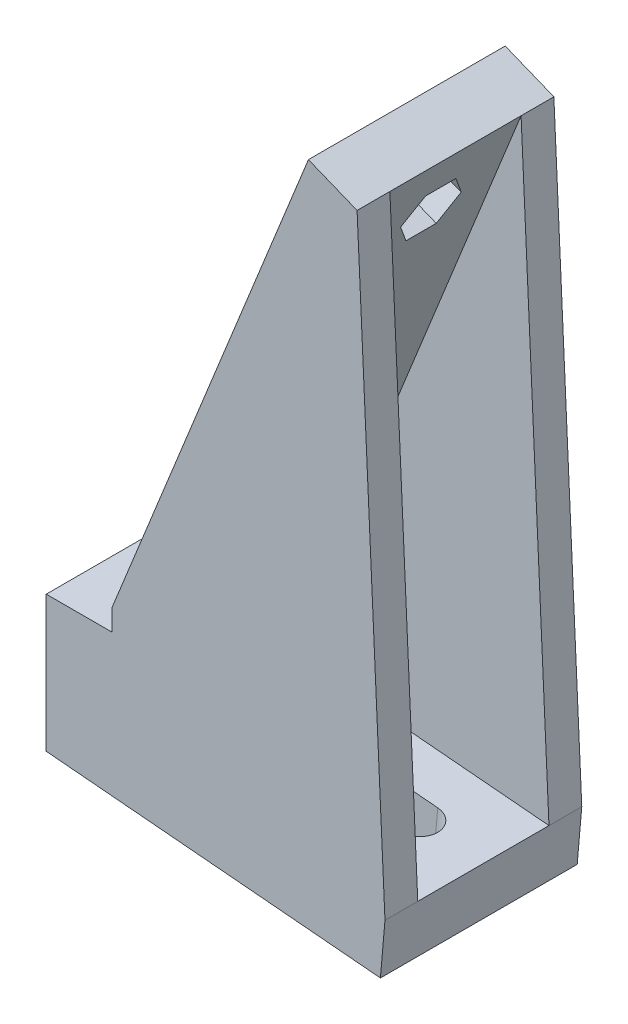
SolidWorks part; units mm, degrees
ref_plane "Front Plane" through (0, 0, 0) normal (0, 0, 1) x (1, 0, 0)
ref_plane "Top Plane" through (0, 0, 0) normal (0, 1, 0) x (1, 0, 0)
ref_plane "Right Plane" through (0, 0, 0) normal (1, 0, 0) x (0, 0, -1)
sketch "Sketch1" plane through (0, 0, 0) normal (0, 0, 1) x (1, 0, 0)
  line L0 (0, 0) -> (29.9685, 74.1747)
  line L3 (65.2738, -16.9226) -> (1.7911, -16.9226) construction
  line L4 (1.7911, -16.9226) -> (37.386, 71.1779)
  line L5 (37.386, 71.1779) -> (29.9685, 74.1747)
  line L7 (0, 0) -> (0, -3.175)
  line L8 (0, -3.175) -> (-10, -3.175)
  line L9 (0, -3.175) -> (-280, -3.175) construction
  line L10 (-10, -3.175) -> (-10, -23.9215)
  line L11 (194.4997, -41.8129) -> (-483.4753, 17.5022) construction
  line L12 (-10, -23.9215) -> (40.9417, -28.3783)
  line L13 (40.9417, -28.3783) -> (41.6389, -20.4088)
  line L15 (1.7911, -16.9226) -> (41.6389, -20.4088)
  dimension "D1" = 8
  dimension "D2" = 68
  dimension "D3" = 8
  dimension "D4" = 80
  dimension "D5" = 10
  dimension "D6" = 40
extrude "Boss-Extrude1" add sketch "Sketch1" along normal mid plane 30
sketch "Sketch2" plane through (-1.0772, -16.6716, 0) normal (0.0872, 0.9962, 0) x (0.9962, -0.0872, 0)
  line L0 (32.8793, 0) -> (27.8793, 0) construction
  line L1 (32.8793, -3) -> (27.8793, -3)
  line L2 (32.8793, 3) -> (27.8793, 3)
  line L4 (42.8793, -15) -> (42.8793, 15) construction
  arc A0 (32.8793, -3) -> (32.8793, 3) centre (32.8793, 0) ccw
  arc A1 (27.8793, 3) -> (27.8793, -3) centre (27.8793, 0) ccw
  point P3 (30.3793, 0)
  dimension "D3" = 3
  dimension "D1" = 5
  dimension "D2" = 10
extrude "Cut-Extrude1" cut sketch "Sketch2" against normal through all
sketch "Sketch3" plane through (7.4175, -2.9969, 0) normal (0.9272, -0.3746, 0) x (0, 0, -1)
sketch "Sketch4" plane through (0, 0, 15) normal (0, 0, 1) x (1, 0, 0)
  line L0 (37.386, 71.1779) -> (41.6389, -20.4088)
  line L1 (40.9417, -28.3783) -> (41.6389, -20.4088) construction
  line L2 (41.6389, -20.4088) -> (1.7911, -16.9226) construction
rib "Rib1" sketch "Sketch4" sketch "Sketch4" thickness 5 extrusion direction parallel to sketch draft on no parameters "D1"=5
mirror "Mirror1" about plane through (0, 0, 0) normal (0, 0, 1) of "Rib1"
sketch "Sketch6" plane through (7.4175, -2.9969, 0) normal (0.9272, -0.3746, 0) x (0, 0, -1)
  line L0 (-10, 80) -> (10, 80) construction
  point P0 (0, 70)
  point P2 (0, 25)
  point P9 (0, 80)
  dimension "D1" = 10
  dimension "D2" = 45
hole_wizard "M4 Clearance Hole1" positions "Sketch6" profile "Sketch7" hole size "M4" standard "ANSI Metric" end condition through all
sketch "Sketch7" plane through (33.6399, 61.906, 0) normal (0, 0, 1) x (0.3746, 0.9272, 0)
  line L0 (0, 0) -> (0, 45.0582)
  line L1 (0, 45.0582) -> (2.25, 45.0582)
  line L2 (2.25, 45.0582) -> (2.25, 0.025)
  line L3 (2.25, 0.025) -> (2.275, 0)
  line L5 (2.275, 0) -> (0, 0)
  line L6 (-2.25, 0.025) -> (-2.275, 0) construction
  line L11 (0, -6.35) -> (0, 107.95) construction
  dimension "Thru Hole Dia." = 4.5
  dimension "Thru Hole Depth" = 45.0582
  dimension "Near C'Sink Dia." = 4.55
  dimension "Near C'Sink Angle" = 90
sketch "Sketch8" plane through (7.4175, -2.9969, 0) normal (0.9272, -0.3746, 0) x (0, 0, -1)
  line L1 (4.6188, 70) -> (2.3094, 74)
  line L2 (2.3094, 74) -> (-2.3094, 74)
  line L3 (-2.3094, 74) -> (-4.6188, 70)
  line L4 (-4.6188, 70) -> (-2.3094, 66)
  line L5 (-2.3094, 66) -> (2.3094, 66)
  line L6 (2.3094, 66) -> (4.6188, 70)
  line L7 (4.6188, 25) -> (2.3094, 29)
  line L8 (2.3094, 29) -> (-2.3094, 29)
  line L9 (-2.3094, 29) -> (-4.6188, 25)
  line L10 (-4.6188, 25) -> (-2.3094, 21)
  line L11 (-2.3094, 21) -> (2.3094, 21)
  line L12 (2.3094, 21) -> (4.6188, 25)
  circle A0 centre (0, 70) radius 4 construction
  circle A1 centre (0, 25) radius 4 construction
  dimension "D1" = 8
  dimension "D2" = 8
extrude "Cut-Extrude2" cut sketch "Sketch8" against normal blind 3
fillet "Fillet1" radius 10 1 edges at (1.7911, -16.9226, 0)
sketch "Sketch11" plane through (0, 0, 15) normal (0, 0, 1) x (1, 0, 0)
  line L0 (-10, -3.175) -> (-10, 0)
  line L1 (-10, 0) -> (-3.4243, 0)
  line L2 (-3.4243, 0) -> (27.0247, 75.3641)
  line L3 (27.0247, 75.3641) -> (29.9685, 74.1747)
  line L4 (29.9685, 74.1747) -> (0, 0) construction
  line L5 (-10, -3.175) -> (0, -3.175)
  line L6 (0, -3.175) -> (0, 0)
  line L7 (0, 0) -> (29.9685, 74.1747)
  dimension "D1" = 3.175
extrude "Boss-Extrude2" [suppressed] add sketch "Sketch11" against normal blind 4
